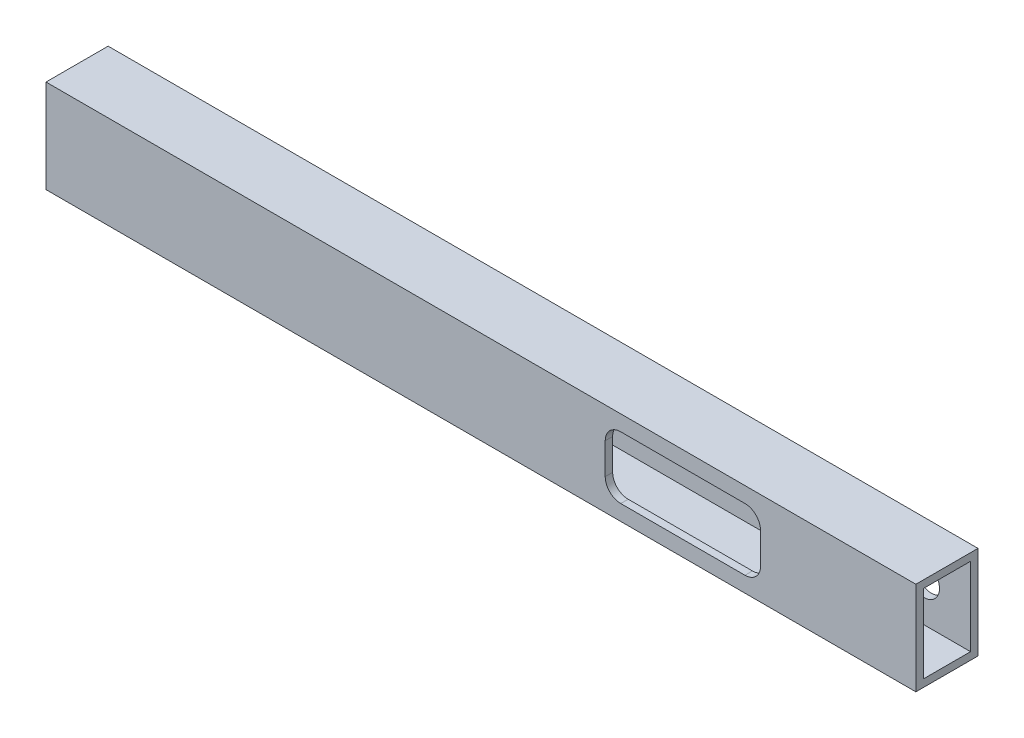
SolidWorks part; units mm, degrees
material "AISI 1010 Steel, hot rolled bar"
ref_plane "Front Plane" through (0, 0, 0) normal (0, 0, 1) x (1, 0, 0)
ref_plane "Top Plane" through (0, 0, 0) normal (0, 1, 0) x (1, 0, 0)
ref_plane "Right Plane" through (0, 0, 0) normal (1, 0, 0) x (0, 0, -1)
sketch "Sketch1" plane through (0, 0, 0) normal (1, 0, 0) x (0, 0, -1)
  line L0 (-9.652, 16.002) -> (9.652, 16.002)
  line L1 (-12.7, -19.05) -> (12.7, -19.05)
  line L2 (-12.7, -19.05) -> (-12.7, 19.05)
  line L3 (-12.7, 19.05) -> (12.7, 19.05)
  line L4 (12.7, -19.05) -> (12.7, 19.05)
  line L5 (-12.7, -19.05) -> (12.7, 19.05) construction
  line L6 (-12.7, 19.05) -> (12.7, -19.05) construction
  line L7 (9.652, -16.002) -> (9.652, 16.002)
  line L8 (-9.652, -16.002) -> (9.652, -16.002)
  line L9 (-9.652, -16.002) -> (-9.652, 16.002)
  point P0 (0, 0)
  dimension "D1" = 25.4
  dimension "D2" = 38.1
  dimension "D3" = 3.048
extrude "Boss-Extrude1" add sketch "Sketch1" along normal blind 355.6
sketch "Sketch2" plane through (0, 0, -12.7) normal (0, 0, -1) x (-1, 0, 0)
  line L0 (-355.6, 0) -> (0, 0) construction
  line L1 (-355.6, -19.05) -> (-355.6, 19.05) construction
  circle A0 centre (-336.55, 0) radius 6.35
  dimension "D2" = 12.7
  dimension "D1" = 19.05
extrude "Cut-Extrude1" cut sketch "Sketch2" against normal up to next
sketch "Sketch3" plane through (0, 0, -12.7) normal (0, 0, -1) x (-1, 0, 0)
  line L0 (0, 0) -> (-355.6, 0) construction
  line L1 (-355.6, -19.05) -> (-355.6, 19.05) construction
  circle A0 centre (-260.35, 0) radius 3.175
  circle A1 centre (-336.55, 0) radius 6.35 construction
  dimension "D1" = 76.2
  dimension "D2" = 6.35
extrude "Cut-Extrude2" cut sketch "Sketch3" against normal up to next
sketch "Sketch4" plane through (0, 0, 12.7) normal (0, 0, 1) x (1, 0, 0)
  line L0 (0, 0) -> (355.6, 0) construction
  line L1 (234.95, -12.7) -> (285.75, -12.7)
  line L2 (228.6, -6.35) -> (228.6, 6.35)
  line L3 (234.95, 12.7) -> (285.75, 12.7)
  line L4 (292.1, -6.35) -> (292.1, 6.35)
  line L5 (228.6, -12.7) -> (292.1, 12.7) construction
  line L6 (228.6, 12.7) -> (292.1, -12.7) construction
  line L7 (355.6, 19.05) -> (355.6, -19.05) construction
  arc A0 (285.75, 12.7) -> (292.1, 6.35) centre (285.75, 6.35) cw
  arc A1 (285.75, -12.7) -> (292.1, -6.35) centre (285.75, -6.35) ccw
  arc A2 (234.95, -12.7) -> (228.6, -6.35) centre (234.95, -6.35) cw
  arc A3 (228.6, 6.35) -> (234.95, 12.7) centre (234.95, 6.35) cw
  point P0 (260.35, 0)
  dimension "D4" = 6.35
  dimension "D1" = 63.5
  dimension "D2" = 25.4
  dimension "D3" = 63.5
extrude "Cut-Extrude3" cut sketch "Sketch4" against normal up to next
